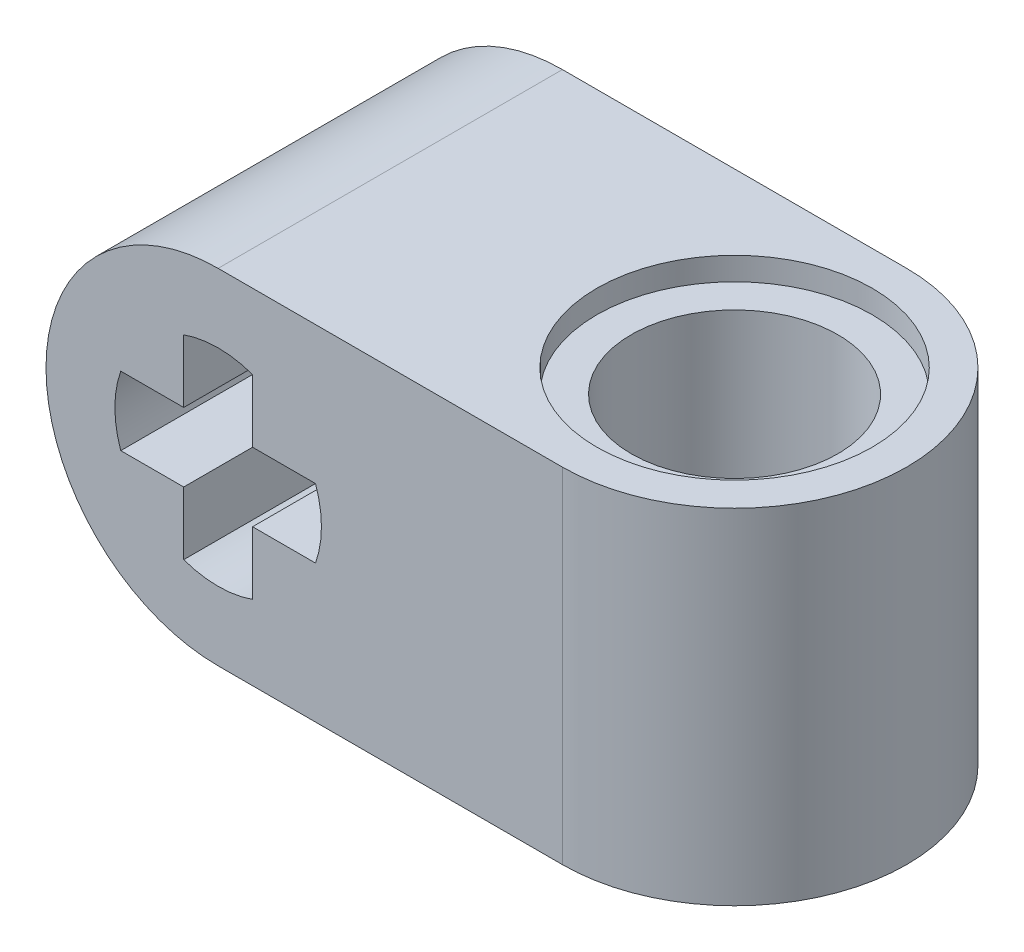
SolidWorks part; units mm, degrees
ref_plane "Front Plane" through (0, 0, 0) normal (0, 0, 1) x (1, 0, 0)
ref_plane "Top Plane" through (0, 0, 0) normal (0, 1, 0) x (1, 0, 0)
ref_plane "Right Plane" through (0, 0, 0) normal (1, 0, 0) x (0, 0, -1)
sketch "Sketch1" plane through (0, 0, 0) normal (0, 1, 0) x (1, 0, 0)
  line L1 (-5, -2.5) -> (5, -2.5)
  line L2 (-5, -2.5) -> (-5, 2.5)
  line L3 (-5, 2.5) -> (5, 2.5)
  line L4 (5, -2.5) -> (5, 2.5)
  line L5 (-5, -2.5) -> (5, 2.5) construction
  line L6 (-5, 2.5) -> (5, -2.5) construction
  circle A0 centre (2.5, 0) radius 2.5
  circle A1 centre (2.5, 0) radius 1.5
  circle A2 centre (2.5, 0) radius 2
  point P0 (0, 0)
  dimension "D3" = 4
  dimension "D4" = 3
  dimension "D1" = 10
  dimension "D2" = 5
extrude "Boss-Extrude1" add sketch "Sketch1" along normal blind 5 contours A0 L3 L2 L1 | A0 A2 | A2 A1 region at (-2.2036, 0, 0) region at (0.0707, 0, 0) region at (0.5566, 0, 0)
extrude "Cut-Extrude1" cut sketch "Sketch1<3>" along normal blind 0.3333 contours A2 A1 region at (0.5566, 0, 0)
sketch "Sketch1<3>" plane through (0, 0, 0) normal (0, 1, 0) x (1, 0, 0) same geometry as "Sketch1"
sketch "Sketch2" plane through (0, 5, 0) normal (0, 1, 0) x (1, 0, 0)
  circle A0 centre (2.5, 0) radius 1.5
  circle A1 centre (2.5, 0) radius 2
  dimension "D1" = 4
extrude "Cut-Extrude2" cut sketch "Sketch2" against normal blind 0.3333
sketch "Sketch3" plane through (0, 0, 2.5) normal (0, 0, 1) x (1, 0, 0)
  line L1 (-5, 5) -> (2.5, 5)
  line L2 (-5, 5) -> (-5, 0)
  line L3 (-5, 0) -> (2.5, 0)
  line L4 (2.5, 5) -> (2.5, 0)
  line L5 (-3, 1) -> (-2, 1)
  line L6 (-3, 1) -> (-3, 4)
  line L7 (-3, 4) -> (-2, 4)
  line L8 (-2, 1) -> (-2, 4)
  line L9 (-3, 1) -> (-2, 4) construction
  line L10 (-3, 4) -> (-2, 1) construction
  line L11 (-4, 2) -> (-1, 2)
  line L12 (-4, 2) -> (-4, 3)
  line L13 (-4, 3) -> (-1, 3)
  line L14 (-1, 2) -> (-1, 3)
  line L15 (-4, 2) -> (-1, 3) construction
  line L16 (-4, 3) -> (-1, 2) construction
  circle A0 centre (-2.5, 2.5) radius 2.5
  circle A1 centre (-2.5, 2.5) radius 1.5
  line M5 (-5, 0) -> (2.5, 0)
  line M8 (-5, 5) -> (-5, 0)
  dimension "D1" = 1
  dimension "D2" = 3
extrude "Cut-Extrude3" cut sketch "Sketch3" against normal up to next contours A0 L1 M8 | A0 L2 M5 | L13 A1 L11 L6 | L8 A1 L6 L13 | L13 L6 L11 L8 | A1 L13 L8 L11 | L6 A1 L8 L11 region at (-4.4416, 4.4416, 2.5) region at (-4.4416, 0.5584, 2.5) region at (-2.5, 1.5138, 2.5) region at (-3.4862, 2.5, 2.5) region at (-2.5, 2.5, 2.5) region at (-1.5138, 2.5, 2.5) region at (-2.5, 3.4862, 2.5)
